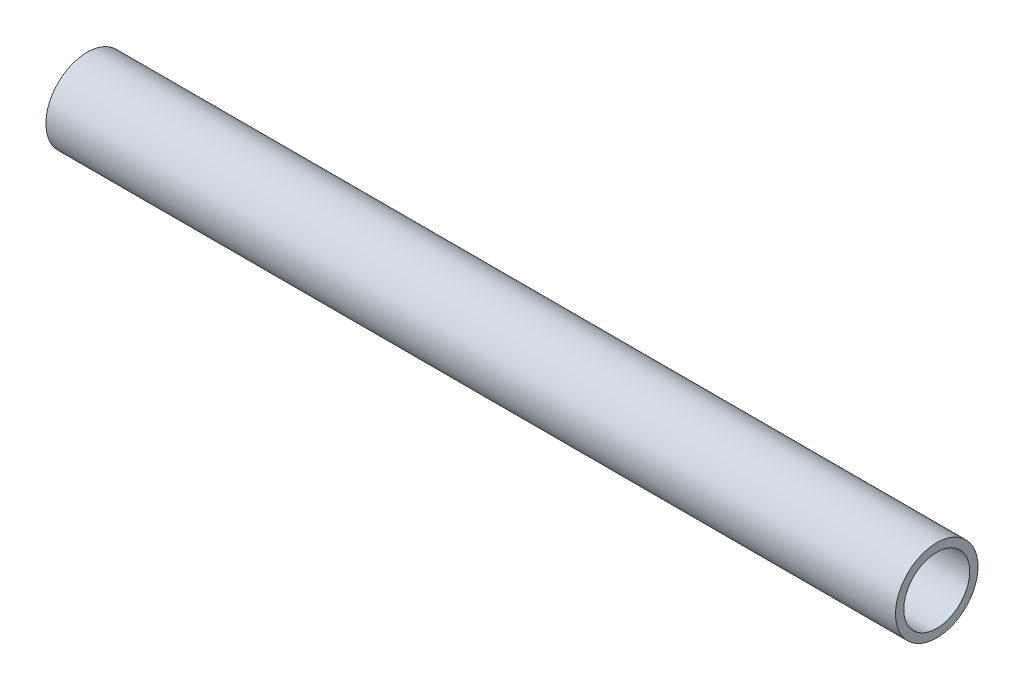
SolidWorks part; units mm, degrees
material "PC High Viscosity"
ref_plane "Front Plane" through (0, 0, 0) normal (0, 0, 1) x (1, 0, 0)
ref_plane "Top Plane" through (0, 0, 0) normal (0, 1, 0) x (1, 0, 0)
ref_plane "Right Plane" through (0, 0, 0) normal (1, 0, 0) x (0, 0, -1)
sketch "Sketch1" plane through (0, 0, 0) normal (1, 0, 0) x (0, 0, -1)
  circle A0 centre (0, 0) radius 15.875
  dimension "D1" = 31.75
extrude "Extrude-Thin1" add sketch "Sketch1" along normal mid plane 326.9932 thin thin type one direction reverse wall 3.175
